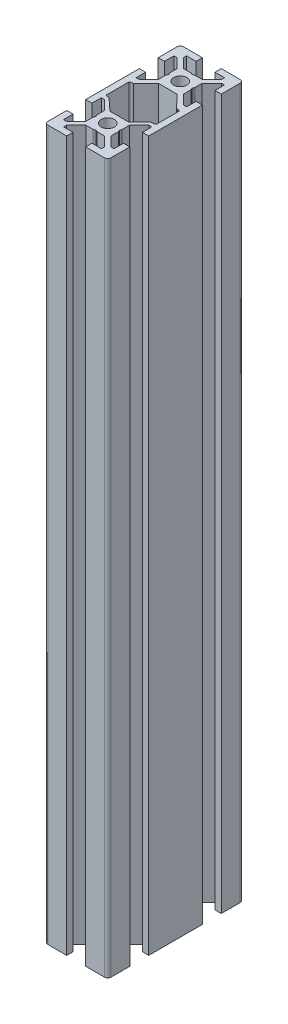
SolidWorks part; units mm, degrees
material "6063-T5"
ref_plane "Top Plane" through (0, 0, 0) normal (0, 0, 1) x (1, 0, 0)
ref_plane "Front Plane" through (0, 0, 0) normal (0, 1, 0) x (1, 0, 0)
ref_plane "Side Plane" through (0, 0, 0) normal (1, 0, 0) x (0, 0, -1)
sketch "Sketch3" plane through (0, 0, 0) normal (0, 1, 0) x (1, 0, 0)
  line L0 (-13.8894, 24) -> (-15.1622, 23.8)
  line L1 (-15.7622, 23.6) -> (-15.7622, 9.279)
  line L2 (-15.1622, 8.679) -> (-13.8894, 8.679)
  line L3 (-13.4651, 8.5033) -> (-5.6408, 1.321)
  line L4 (-5.6408, 1.321) -> (6.0854, 1.321)
  line L5 (6.0854, 1.321) -> (12.9275, 8.3595)
  line L6 (15.1167, 8.3595) -> (15.3559, 8.3717)
  line L7 (16.2378, 9.279) -> (16.2067, 23.6)
  line L8 (16.2067, 23.6) -> (14.3651, 24)
  line L9 (13.9408, 24) -> (6.1165, 32)
  line L10 (-5.6408, 32) -> (-13.4651, 24)
  line L11 (6.1165, 32) -> (-5.6408, 32)
  line L12 (-19.7933, 34.0345) -> (-19.7933, 0.0345)
  line L13 (-19.7933, 0.0345) -> (-15.7933, 0.0345)
  line L14 (-15.7933, 0.0345) -> (-15.7933, 6.0345)
  line L15 (-15.7933, 6.0345) -> (-13.9146, 6.0345)
  line L16 (-13.9146, 6.0345) -> (-7.7933, -0.0869)
  line L17 (-7.7933, -0.0869) -> (-7.7933, -0.9655)
  line L18 (-7.7933, -0.9655) -> (-7.7933, -4.6584)
  line L20 (-7.6593, -5.1584) -> (-7.1933, -5.9655)
  line L21 (-7.1933, -5.9655) -> (-7.6593, -6.7727)
  line L22 (-7.7933, -7.2727) -> (-7.7933, -11.8442)
  line L23 (-7.7933, -11.8442) -> (-13.9146, -17.9655)
  line L24 (-13.9146, -17.9655) -> (-15.7933, -17.9655)
  line L25 (-15.7933, -17.9655) -> (-15.7933, -11.9655)
  line L26 (-15.7933, -11.9655) -> (-19.7933, -11.9655)
  line L27 (-19.7933, -11.9655) -> (-19.7933, -23.9655)
  line L28 (-17.7933, -25.9655) -> (-5.7933, -25.9655)
  line L29 (-5.7933, -25.9655) -> (-5.7933, -21.9655)
  line L30 (-5.7933, -21.9655) -> (-11.7933, -21.9655)
  line L31 (-11.7933, -21.9655) -> (-11.7933, -20.0869)
  line L32 (-11.7933, -20.0869) -> (-5.672, -13.9655)
  line L33 (-5.672, -13.9655) -> (-4.7933, -13.9655)
  line L34 (-4.7933, -13.9655) -> (-1.1005, -13.9655)
  line L36 (-0.6005, -13.8316) -> (0.2067, -13.3655)
  line L37 (0.2067, -13.3655) -> (1.0139, -13.8316)
  line L38 (1.5139, -13.9655) -> (6.0854, -13.9655)
  line L39 (6.0854, -13.9655) -> (12.2067, -20.0869)
  line L40 (12.2067, -20.0869) -> (12.2067, -21.9655)
  line L41 (12.2067, -21.9655) -> (6.2067, -21.9655)
  line L42 (6.2067, -21.9655) -> (6.2067, -25.9655)
  line L43 (6.2067, -25.9655) -> (18.2067, -25.9655)
  line L44 (20.2067, -23.9655) -> (20.2067, -11.9655)
  line L45 (20.2067, -11.9655) -> (16.2067, -11.9655)
  line L46 (16.2067, -11.9655) -> (16.2067, -17.9655)
  line L47 (16.2067, -17.9655) -> (14.328, -17.9655)
  line L48 (14.328, -17.9655) -> (8.2067, -11.8442)
  line L49 (8.2067, -11.8442) -> (8.2067, -10.9655)
  line L50 (8.2067, -10.9655) -> (8.2067, -7.2727)
  line L52 (8.0727, -6.7727) -> (7.6067, -5.9655)
  line L53 (7.6067, -5.9655) -> (8.0727, -5.1584)
  line L54 (8.2067, -4.6584) -> (8.2067, -0.0869)
  line L55 (8.2067, -0.0869) -> (14.328, 6.0345)
  line L56 (14.328, 6.0345) -> (16.2067, 6.0345)
  line L57 (16.2067, 6.0345) -> (16.2067, 0.0345)
  line L58 (16.2067, 0.0345) -> (20.2067, 0.0345)
  line L59 (20.2067, 0.0345) -> (20.2067, 34.0345)
  line L60 (20.2067, 34.0345) -> (16.2067, 34.0345)
  line L61 (16.2067, 34.0345) -> (16.2067, 28.0345)
  line L62 (16.2067, 28.0345) -> (14.328, 28.0345)
  line L63 (14.328, 28.0345) -> (8.2067, 34.1558)
  line L64 (8.2067, 34.1558) -> (8.2067, 38.7273)
  line L65 (8.0727, 39.2273) -> (7.6067, 40.0345)
  line L66 (7.6067, 40.0345) -> (8.0727, 40.8416)
  line L68 (8.2067, 41.3416) -> (8.2067, 45.0345)
  line L69 (8.2067, 45.0345) -> (8.2067, 45.9131)
  line L70 (8.2067, 45.9131) -> (14.328, 52.0345)
  line L71 (14.328, 52.0345) -> (16.2067, 52.0345)
  line L72 (16.2067, 52.0345) -> (16.2067, 46.0345)
  line L73 (16.2067, 46.0345) -> (20.2067, 46.0345)
  line L74 (20.2067, 46.0345) -> (20.2067, 58.0345)
  line L75 (18.2067, 60.0345) -> (6.2067, 60.0345)
  line L76 (6.2067, 60.0345) -> (6.2067, 56.0345)
  line L77 (6.2067, 56.0345) -> (12.2067, 56.0345)
  line L78 (12.2067, 56.0345) -> (12.2067, 54.1558)
  line L79 (12.2067, 54.1558) -> (6.0854, 48.0345)
  line L80 (6.0854, 48.0345) -> (1.5139, 48.0345)
  line L81 (1.0139, 47.9005) -> (0.2067, 47.4345)
  line L82 (0.2067, 47.4345) -> (-0.6005, 47.9005)
  line L84 (-1.1005, 48.0345) -> (-4.7933, 48.0345)
  line L85 (-4.7933, 48.0345) -> (-5.672, 48.0345)
  line L86 (-5.672, 48.0345) -> (-11.7933, 54.1558)
  line L87 (-11.7933, 54.1558) -> (-11.7933, 56.0345)
  line L88 (-11.7933, 56.0345) -> (-5.7933, 56.0345)
  line L89 (-5.7933, 56.0345) -> (-5.7933, 60.0345)
  line L90 (-5.7933, 60.0345) -> (-17.7933, 60.0345)
  line L91 (-19.7933, 58.0345) -> (-19.7933, 46.0345)
  line L92 (-19.7933, 46.0345) -> (-15.7933, 46.0345)
  line L93 (-15.7933, 46.0345) -> (-15.7933, 52.0345)
  line L94 (-15.7933, 52.0345) -> (-13.9146, 52.0345)
  line L95 (-13.9146, 52.0345) -> (-7.7933, 45.9131)
  line L96 (-7.7933, 45.9131) -> (-7.7933, 41.3416)
  line L97 (-7.6593, 40.8416) -> (-7.1933, 40.0345)
  line L98 (-7.1933, 40.0345) -> (-7.6593, 39.2273)
  line L100 (-7.7933, 38.7273) -> (-7.7933, 35.0345)
  line L101 (-7.7933, 35.0345) -> (-7.7933, 34.1558)
  line L102 (-7.7933, 34.1558) -> (-13.9146, 28.0345)
  line L103 (-13.9146, 28.0345) -> (-15.7933, 28.0345)
  line L104 (-15.7933, 28.0345) -> (-15.7933, 34.0345)
  line L105 (-15.7933, 34.0345) -> (-19.7933, 34.0345)
  line L106 (15.3559, 8.3717) -> (16.2378, 9.279)
  line L109 (-15.1622, 8.679) -> (-15.7622, 9.279)
  line L112 (12.9275, 8.3595) -> (15.1167, 8.3595)
  arc A0 (-3.9796, -5.9655) -> (4.4204, -5.9655) centre (0.2204, -5.9655) ccw
  arc A1 (4.4204, -5.9655) -> (-3.9796, -5.9655) centre (0.2204, -5.9655) ccw
  arc A2 (-15.1622, 23.8) -> (-15.7622, 23.6) centre (-14.4699, 20.7231) ccw
  arc A3 (-13.8894, 24) -> (-13.4651, 24) centre (-13.6772, 27.3395) ccw
  arc A4 (-7.7933, -4.6584) -> (-7.6593, -5.1584) centre (-6.7933, -4.6584) ccw
  arc A5 (-7.6593, -6.7727) -> (-7.7933, -7.2727) centre (-6.7933, -7.2727) ccw
  arc A6 (-19.7933, -23.9655) -> (-17.7933, -25.9655) centre (-17.7933, -23.9655) ccw
  arc A7 (-1.1005, -13.9655) -> (-0.6005, -13.8316) centre (-1.1005, -12.9655) ccw
  arc A8 (1.0139, -13.8316) -> (1.5139, -13.9655) centre (1.5139, -12.9655) ccw
  arc A9 (18.2067, -25.9655) -> (20.2067, -23.9655) centre (18.2067, -23.9655) ccw
  arc A10 (8.2067, -7.2727) -> (8.0727, -6.7727) centre (7.2067, -7.2727) ccw
  arc A11 (8.0727, -5.1584) -> (8.2067, -4.6584) centre (7.2067, -4.6584) ccw
  arc A12 (8.2067, 38.7273) -> (8.0727, 39.2273) centre (7.2067, 38.7273) ccw
  arc A13 (8.0727, 40.8416) -> (8.2067, 41.3416) centre (7.2067, 41.3416) ccw
  arc A14 (20.2067, 58.0345) -> (18.2067, 60.0345) centre (18.2067, 58.0345) ccw
  arc A15 (1.5139, 48.0345) -> (1.0139, 47.9005) centre (1.5139, 47.0345) ccw
  arc A16 (-0.6005, 47.9005) -> (-1.1005, 48.0345) centre (-1.1005, 47.0345) ccw
  arc A17 (-17.7933, 60.0345) -> (-19.7933, 58.0345) centre (-17.7933, 58.0345) ccw
  arc A18 (-7.7933, 41.3416) -> (-7.6593, 40.8416) centre (-6.7933, 41.3416) ccw
  arc A19 (-7.6593, 39.2273) -> (-7.7933, 38.7273) centre (-6.7933, 38.7273) ccw
  arc A21 (-13.4651, 8.5033) -> (-13.8894, 8.679) centre (-14.7912, 5.9019) ccw
  arc A25 (13.9408, 24) -> (14.3651, 24) centre (14.1529, 27.3395) ccw
  arc A26 (-3.9933, 40.0345) -> (4.4067, 40.0345) centre (0.2067, 40.0345) ccw
  arc A27 (4.4067, 40.0345) -> (-3.9933, 40.0345) centre (0.2067, 40.0345) ccw
  point P15 (7.2067, 1.321)
  point P16 (0, 0)
  point P52 (6.0854, 1.321)
  point P57 (11.3234, 7.3566)
  point P77 (16.2067, 23.8)
  point P84 (0, 0)
  point P85 (15.8007, 23.6)
  point P91 (13.9408, 8.2992)
  point P94 (0, 0)
  point P117 (15.6185, 8.3852)
  point P136 (0, 0)
  point P155 (0, 0)
  point P162 (0, 0)
  point P163 (12.9275, 8.3595)
  point P164 (0, 0)
  point P165 (0, 0)
  dimension "D1" = 40
  dimension "D2" = 36
  dimension "D3" = 14
  dimension "D4" = 34
  dimension "D5" = 34
  dimension "D6" = 46
extrude "Boss-Extrude3" add sketch "Sketch3" along normal blind 450
